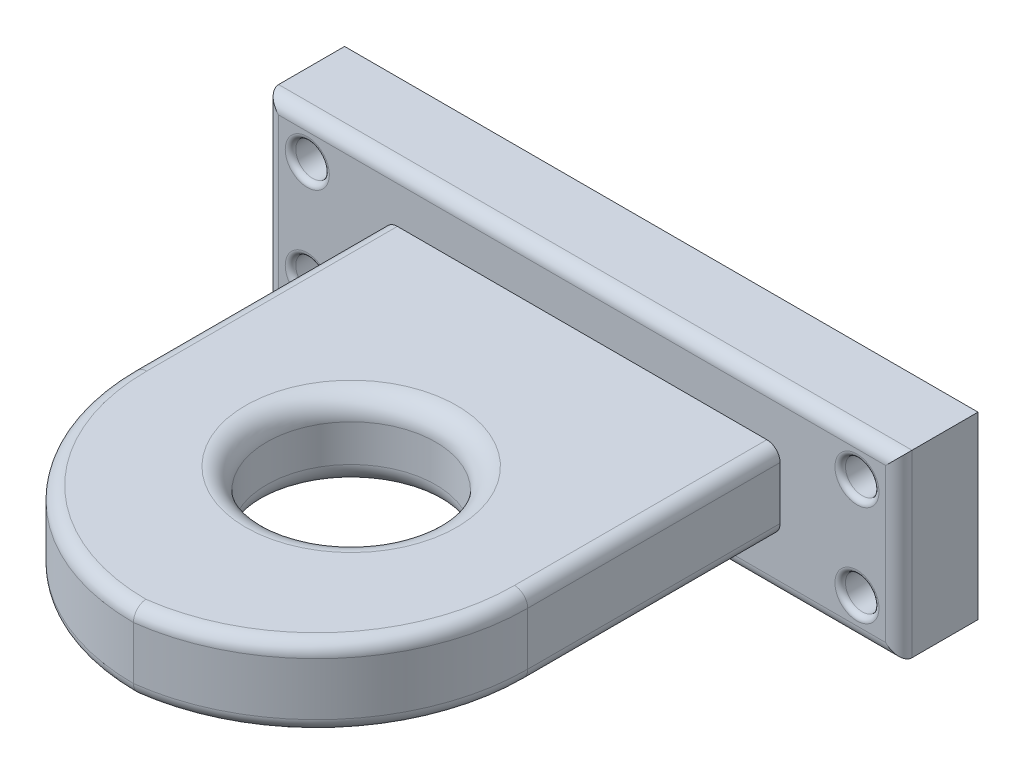
SolidWorks part; units mm, degrees
ref_plane "Front Plane" through (0, 0, 0) normal (0, 0, 1) x (1, 0, 0)
ref_plane "Top Plane" through (0, 0, 0) normal (0, 1, 0) x (1, 0, 0)
ref_plane "Right Plane" through (0, 0, 0) normal (1, 0, 0) x (0, 0, -1)
sketch "Sketch1" plane through (0, 0, 0) normal (0, 1, 0) x (1, 0, 0)
  line L1 (0, 0) -> (150, 0)
  line L2 (0, 0) -> (0, -175)
  line L3 (0, -175) -> (150, -175)
  line L4 (150, 0) -> (150, -175)
  dimension "D1" = 150
  dimension "D2" = 175
extrude "Boss-Extrude1" add sketch "Sketch1" along normal blind 30
sketch "Sketch3" plane through (0, 30, 0) normal (0, 1, 0) x (-1, 0, 0)
  circle A0 centre (-75, 87.5) radius 32
  dimension "D1" = 64
extrude "Cut-Extrude2" cut sketch "Sketch3" against normal through all
fillet "Fillet1" radius 80 1 edges at (0, 15, 175)
fillet "Fillet2" radius 80 1 edges at (150, 15, 175)
fillet "Fillet3" radius 8 1 edges at (75, 30, 119.5)
fillet "Fillet4" radius 8 1 edges at (75, 0, 119.5)
sketch "Sketch5" plane through (0, 0, 0) normal (0, 0, -1) x (-1, 0, 0)
  line L0 (-150, 30) -> (-150, 0) construction
  line L1 (-195, 49.05) -> (45, 49.05)
  line L2 (-195, 49.05) -> (-195, -19.05)
  line L3 (-195, -19.05) -> (45, -19.05)
  line L4 (45, 49.05) -> (45, -19.05)
  line L5 (-150, 30) -> (0, 30) construction
  line L6 (0, 30) -> (0, 0) construction
  line L7 (-150, 0) -> (0, 0) construction
  dimension "D1" = 45
  dimension "D2" = 45
  dimension "D3" = 19.05
  dimension "D4" = 19.05
extrude "Boss-Extrude5" add sketch "Sketch5" along normal blind 30
fillet "Fillet5" radius 5 4 edges at (75, -19.05, 0) (-45, 15, 0) (75, 49.05, 0) (195, 15, 0)
fillet "Fillet6" radius 5 8 edges at (150, 0, 47.8137) (0, 0, 47.5) (23.4315, 0, 151.5685) (130, 0, 148.5425) (0, 30, 47.5) (150, 30, 47.8137) (23.4315, 30, 151.5685) (130, 30, 148.5425)
sketch "Sketch7" plane through (0, 0, 0) normal (0, 0, 1) x (1, 0, 0)
  line L0 (190, 15) -> (-40, 15) construction
  line L1 (190, -14.05) -> (190, 44.05) construction
  line L2 (-40, 44.05) -> (-40, -14.05) construction
  line L3 (75, -14.05) -> (75, 44.05) construction
  line L4 (-40, -14.05) -> (190, -14.05) construction
  line L5 (190, 44.05) -> (-40, 44.05) construction
  circle A0 centre (179.14, 34.05) radius 6.35
  circle A1 centre (179.14, -4.05) radius 6.35
  circle A2 centre (-29.14, 34.05) radius 6.35
  circle A3 centre (-29.14, -4.05) radius 6.35
  dimension "D1" = 12.7
  dimension "D2" = 208.28
  dimension "D3" = 38.1
extrude "Cut-Extrude3" cut sketch "Sketch7" against normal through all
fillet "Fillet7" radius 2 4 edges at (-22.79, -4.05, 0) (-35.49, 34.05, 0) (185.49, 34.05, 0) (172.79, -4.05, 0)
